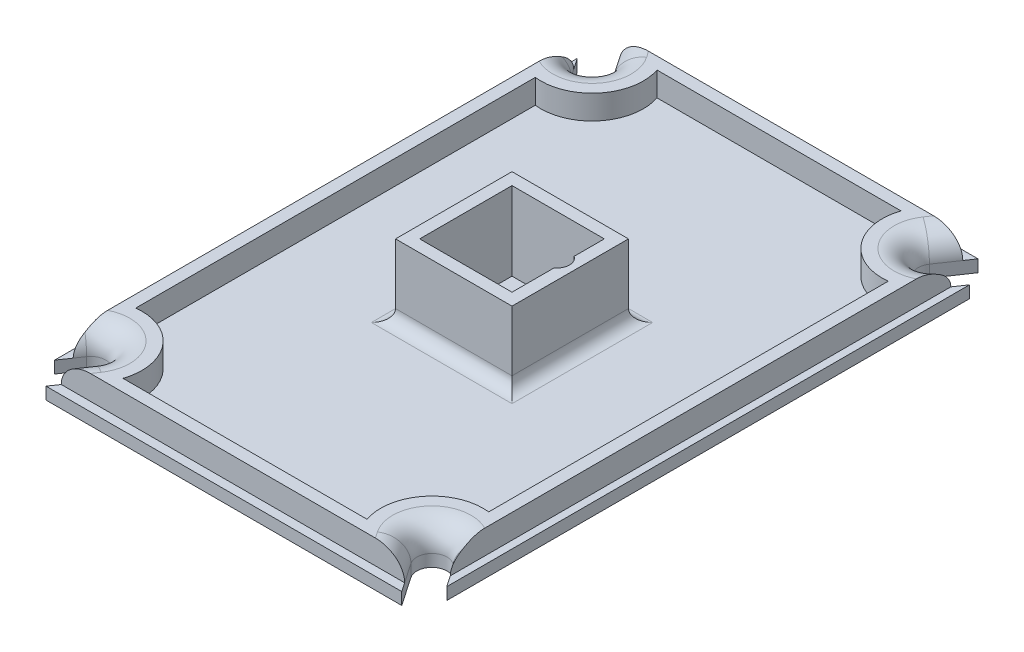
SolidWorks part; units mm, degrees
ref_plane "Front Plane" through (0, 0, 0) normal (0, 0, 1) x (1, 0, 0)
ref_plane "Top Plane" through (0, 0, 0) normal (0, 1, 0) x (1, 0, 0)
ref_plane "Right Plane" through (0, 0, 0) normal (1, 0, 0) x (0, 0, -1)
ref_axis "Axis1" through (0, 14.7, 0) along (0, -1, 0)
sketch "Sketch1" plane through (0, 0, 0) normal (0, 1, 0) x (1, 0, 0)
  line L1 (-31.25, -46.25) -> (31.25, -46.25)
  line L2 (-31.25, -46.25) -> (-31.25, 46.25)
  line L3 (-31.25, 46.25) -> (31.25, 46.25)
  line L4 (31.25, -46.25) -> (31.25, 46.25)
  line L5 (-31.25, -46.25) -> (31.25, 46.25) construction
  line L6 (-31.25, 46.25) -> (31.25, -46.25) construction
  line L7 (-32.5, 47.75) -> (32.5, 47.75)
  line L8 (-32.5, 47.75) -> (-32.5, -47.75)
  line L9 (-32.5, -47.75) -> (32.5, -47.75)
  line L10 (32.5, 47.75) -> (32.5, -47.75)
  line L11 (-32.5, 47.75) -> (32.5, -47.75) construction
  line L12 (-32.5, -47.75) -> (32.5, 47.75) construction
  point P0 (0, 0)
  point P6 (0, 0)
  dimension "D1" = 62.5
  dimension "D2" = 92.5
  dimension "D3" = 65
  dimension "D4" = 95.5
extrude "Boss-Extrude1" add sketch "Sketch1" along normal blind 2 contours L7 L10 L9 L8
extrude "Boss-Extrude2" add sketch "Sketch1<3>" along normal blind 6 contours L1 L4 L3 L2 region at (0, 0, 0)
sketch "Sketch1<3>" plane through (0, 0, 0) normal (0, 1, 0) x (1, 0, 0) same geometry as "Sketch1"
sketch "Sketch2" plane through (0, 0, 0) normal (0, 1, 0) x (1, 0, 0)
  line L0 (7.65, 7.65) -> (7.65, 2.65) construction
  line L1 (-7.65, 7.65) -> (7.65, 7.65)
  line L2 (-7.65, 7.65) -> (-7.65, -7.65)
  line L3 (-7.65, -7.65) -> (7.65, -7.65)
  line L4 (7.65, 7.65) -> (7.65, -7.65)
  line L5 (-7.65, 7.65) -> (7.65, -7.65) construction
  line L6 (-7.65, -7.65) -> (7.65, 7.65) construction
  line L7 (7.65, -7.65) -> (7.65, -0.65) construction
  line L12 (-9.65, -9.65) -> (9.65, -9.65)
  line L13 (9.65, 9.65) -> (9.65, -9.65)
  line L14 (-9.65, 9.65) -> (9.65, 9.65)
  line L15 (-9.65, 9.65) -> (-9.65, -9.65)
  arc A0 (7.65, -0.65) -> (7.65, 2.65) centre (6.5197, 1) ccw
  circle A1 centre (0, 0) radius 7.65
  point P0 (0, 0)
  dimension "D3" = 4
  dimension "D1" = 15.3
  dimension "D2" = 15.3
  dimension "D4" = 5
  dimension "D5" = 7
  dimension "D6" = 2
extrude "Boss-Extrude3" add sketch "Sketch2<4>" along normal blind 8 from surface contours L13 L14 L15 L12 starting at face at (0, 6, 0)
sketch "Sketch2<4>" plane through (0, 0, 0) normal (0, 1, 0) x (1, 0, 0) same geometry as "Sketch2"
extrude "Cut-Extrude1" cut sketch "Sketch2" against normal mid plane 39 contours A1
extrude "Cut-Extrude2" cut sketch "Sketch2<3>" along normal blind 39 from offset 1 contours L4 A0 | L3 L4 L1 L2 region at (8.0053, 0, -1)
sketch "Sketch2<3>" plane through (0, 0, 0) normal (0, 1, 0) x (1, 0, 0) same geometry as "Sketch2"
sketch "Sketch3" plane through (0, 0, 0) normal (0, 1, 0) x (1, 0, 0)
  line L3 (-34.5667, 46.3433) -> (-30.3467, 40.1432)
  line L4 (30.4333, 49.1567) -> (26.2133, 42.9565)
  line L5 (-30.4333, 49.1567) -> (-26.2133, 42.9565)
  line L6 (34.5667, 46.3433) -> (30.3467, 40.1432)
  line L7 (-34.5667, -46.3433) -> (-30.4333, -49.1567)
  line L8 (30.4333, -49.1567) -> (34.5667, -46.3433)
  line L9 (30.4333, 49.1567) -> (34.5667, 46.3433)
  line L10 (-30.4333, 49.1567) -> (-34.5667, 46.3433)
  line L18 (30.3467, -40.1432) -> (34.5667, -46.3433)
  line L20 (0, 23.1046) -> (0, -27.3759) construction
  line L21 (0, -7.7) -> (0, 7.7) construction
  line L22 (26.2133, -42.9565) -> (30.4333, -49.1567)
  line L23 (-26.2133, -42.9565) -> (-30.4333, -49.1567)
  line L24 (-30.3467, -40.1432) -> (-34.5667, -46.3433)
  circle A0 centre (-28.28, 41.5499) radius 2.5
  circle A1 centre (28.28, 41.5499) radius 2.5
  circle A2 centre (-28.28, -41.5499) radius 2.5
  circle A3 centre (28.28, -41.5499) radius 2.5
  point P27 (0, 0)
  dimension "D3" = 5
  dimension "D6" = 5
  dimension "D7" = 5
extrude "Cut-Extrude3" cut sketch "Sketch3" along normal blind 10 contours A2 | A2 L24 L7 L23 | A0 L5 L10 L3 | A0 | A1 L6 L9 L4 | A3 | A3 L22 L8 L18 | A1 region at (-30.9266, 0, -45.4383) region at (-28.28, 0, -41.5499) region at (30.9266, 0, -45.4383) region at (-30.9266, 0, 45.4383) region at (-28.28, 0, 41.5499) region at (30.9266, 0, 45.4383) region at (28.28, 0, 41.5499)
fillet "Fillet1" radius 4 12 edges at (-30.7984, 6, 40.8068) (-27.3341, 6, 44.6033) (27.3341, 6, 44.6033) (30.7984, 6, 40.8068) (30.7984, 6, -40.8068) (27.3341, 6, -44.6033) (-27.3341, 6, -44.6033) (-30.7984, 6, -40.8068) (-26.8733, 6, 39.4832) (26.8733, 6, 39.4832) (26.8733, 6, -39.4832) (-26.8733, 6, -39.4832)
sketch "Sketch5" plane through (0, 6, 0) normal (0, 1, 0) x (1, 0, 0)
  line L8 (9.65, -9.65) -> (-9.65, -9.65) construction
  line L16 (-20.2203, -44.25) -> (20.2203, -44.25)
  line L17 (29.25, -33.1054) -> (29.25, 33.1054)
  line L18 (20.2203, 44.25) -> (-20.2203, 44.25)
  line L19 (-29.25, 33.1054) -> (-29.25, -33.1054)
  line L20 (-20.2203, -44.25) -> (20.2203, -44.25)
  line L21 (29.25, -33.1054) -> (29.25, 33.1054)
  line L22 (20.2203, 44.25) -> (-20.2203, 44.25)
  line L23 (-29.25, 33.1054) -> (-29.25, -33.1054)
  line L26 (9.65, -9.65) -> (-9.65, -9.65)
  line L27 (-9.65, 9.65) -> (-9.65, -9.65) construction
  line L28 (9.65, 9.65) -> (-9.65, 9.65) construction
  line L29 (9.65, 9.65) -> (9.65, -9.65) construction
  line L30 (-9.65, 9.65) -> (-9.65, -9.65)
  line L31 (9.65, 9.65) -> (-9.65, 9.65)
  line L32 (9.65, 9.65) -> (9.65, -9.65)
  arc A8 (-20.2203, -44.25) -> (-29.25, -33.1054) centre (-28.28, -41.5499) ccw
  arc A9 (29.25, -33.1054) -> (20.2203, -44.25) centre (28.28, -41.5499) ccw
  arc A10 (20.2203, 44.25) -> (29.25, 33.1054) centre (28.28, 41.5499) ccw
  arc A11 (-29.25, 33.1054) -> (-20.2203, 44.25) centre (-28.28, 41.5499) ccw
  arc A12 (-20.2203, -44.25) -> (-29.25, -33.1054) centre (-28.28, -41.5499) ccw
  arc A13 (29.25, -33.1054) -> (20.2203, -44.25) centre (28.28, -41.5499) ccw
  arc A14 (20.2203, 44.25) -> (29.25, 33.1054) centre (28.28, 41.5499) ccw
  arc A15 (-29.25, 33.1054) -> (-20.2203, 44.25) centre (-28.28, 41.5499) ccw
  dimension "D1" = 2
extrude "Cut-Extrude5" cut sketch "Sketch5" against normal up to surface (4 mm away) up to face at (0, 2, -47)
fillet "Fillet2" radius 2 4 edges at (0, 2, 9.65) (9.65, 2, 0) (-9.65, 2, 0) (0, 2, -9.65)
